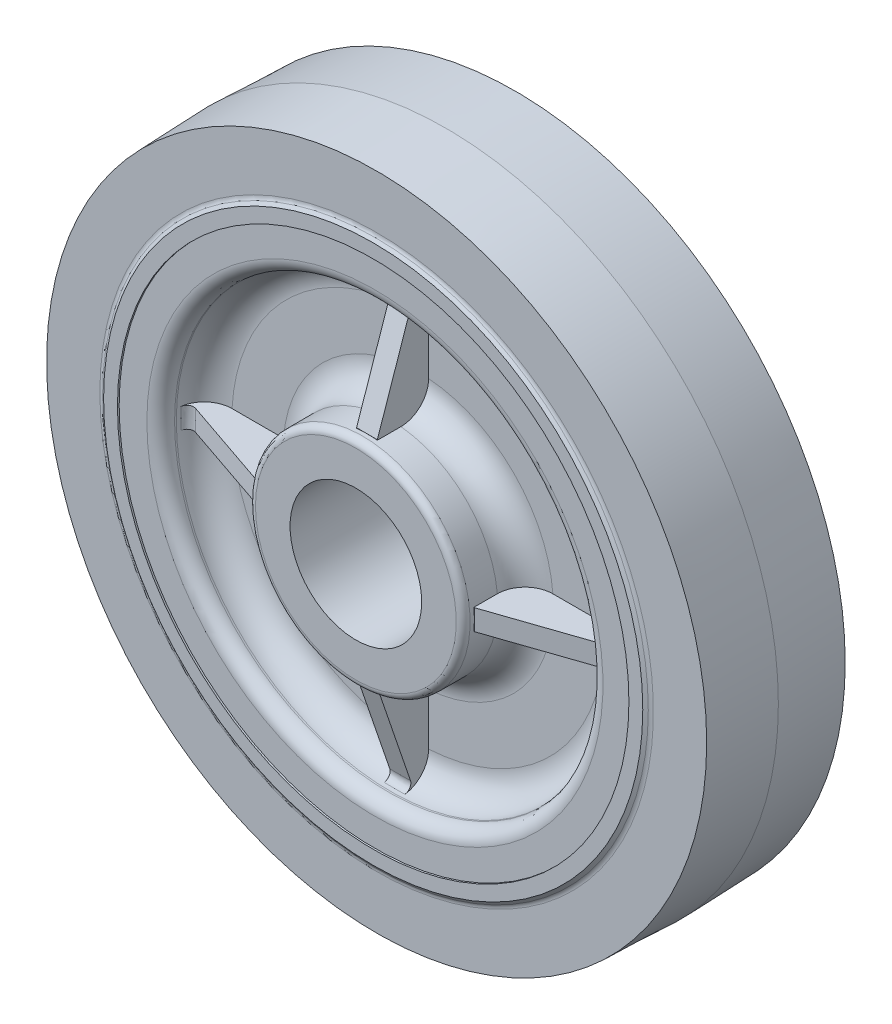
SolidWorks part; units mm, degrees
ref_plane "Front Plane" through (0, 0, 0) normal (0, 0, 1) x (1, 0, 0)
ref_plane "Top Plane" through (0, 0, 0) normal (0, 1, 0) x (1, 0, 0)
ref_plane "Right Plane" through (0, 0, 0) normal (1, 0, 0) x (0, 0, -1)
sketch "Sketch1" plane through (0, 0, 0) normal (1, 0, 0) x (0, 0, -1)
  line L0 (0, 0) -> (41.275, 0) construction
  line L1 (20.6375, 0) -> (20.6375, 76.2) construction
  line L2 (36.9094, 49.0909) -> (26.9875, 49.0909)
  line L3 (26.9875, 28.575) -> (14.2875, 28.575) construction
  line L4 (20.6375, 76.2) -> (36.5125, 75.6456)
  line L5 (36.5125, 75.6456) -> (36.5125, 62.9456)
  line L6 (36.5125, 62.9456) -> (37.3063, 61.7909)
  line L7 (37.3063, 61.7909) -> (37.3063, 58.6159)
  line L8 (37.3063, 58.6159) -> (36.9094, 58.6159)
  line L9 (36.9094, 58.6159) -> (36.9094, 49.0909)
  line L10 (4.3656, 49.0909) -> (14.2875, 49.0909)
  line L11 (14.2875, 49.0909) -> (14.2875, 24.6062)
  line L12 (4.3656, 58.6159) -> (4.3656, 49.0909)
  line L13 (3.9687, 58.6159) -> (4.3656, 58.6159)
  line L14 (3.9687, 61.7909) -> (3.9687, 58.6159)
  line L15 (4.7625, 62.9456) -> (3.9687, 61.7909)
  line L16 (4.7625, 75.6456) -> (4.7625, 62.9456)
  line L17 (26.9875, 49.0909) -> (26.9875, 24.6062)
  line L18 (20.6375, 76.2) -> (4.7625, 75.6456)
  line L19 (0, 15.0812) -> (41.275, 15.0812)
  line L20 (14.2875, 24.6062) -> (0, 24.6062)
  line L21 (0, 15.0812) -> (0, 24.6062)
  line L22 (26.9875, 24.6062) -> (41.275, 24.6062)
  line L23 (41.275, 15.0812) -> (41.275, 24.6062)
  point P9 (20.6375, 28.575)
  dimension "D1" = 41.275
  dimension "D2" = 76.2
  dimension "D3" = 9.525
  dimension "D4" = 12.7
  dimension "D6" = 88
  dimension "D7" = 15.875
  dimension "D8" = 12.7
  dimension "D9" = 0.7937
  dimension "D10" = 0.3969
  dimension "D11" = 3.175
  dimension "D12" = 9.525
  dimension "D13" = 15.0812
revolve "Revolve1" add sketch "Sketch1" angle 360 about L0
fillet "Fillet1" radius 6.35 2 edges at (49.0909, 0, -14.2875) (24.6062, 0, -14.2875)
fillet "Fillet2" radius 3.175 1 edges at (49.0909, 0, -4.3656)
fillet "Fillet3" radius 1.5875 1 edges at (62.9456, 0, -4.7625)
sketch "Sketch2" plane through (0, 0, 0) normal (0, 0, 1) x (1, 0, 0)
  line L1 (0, 0) -> (-76.2, 0) construction
  line L2 (0, 0) -> (0, 76.2) construction
  circle A1 centre (0, 0) radius 76.2 construction
ref_plane "Plane1" through (0, 0, 0) normal (-1, 0, 0) x (0, 0, 1)
sketch "Sketch4" plane through (0, 0, 0) normal (-1, 0, 0) x (0, 0, 1)
  line L1 (-20.6375, 76.2) -> (-20.6375, -76.2) construction
  line L2 (-20.6375, 15.0812) -> (-20.6375, 59.0132)
  line L3 (-2.54, 15.0812) -> (-2.54, 24.6062)
  line L4 (0, 24.6062) -> (-7.9375, 24.6062) construction
  line L5 (0, -24.6062) -> (0, 24.6062) construction
  line L6 (-2.54, 24.6062) -> (-14.2875, 59.0132)
  line L7 (-14.2875, 59.0132) -> (-20.6375, 59.0132)
  line L8 (-2.54, 15.0812) -> (-20.6375, 15.0812)
  dimension "D1" = 2.54
  dimension "D2" = 6.35
  dimension "D3" = 9.525
extrude "Boss-Extrude1" add sketch "Sketch4" along normal blind 2.3813 and the other way blind 2.3813
pattern_circular "CirPattern1" count 4 every 90 about axis through (0, 0, -20.6375) along (0, 0, 1) of "Boss-Extrude1"
fillet "Fillet4" radius 1.5875 4 edges
sketch "Sketch6" plane through (0, 0, 0) normal (-1, 0, 0) x (0, 0, 1)
  line L0 (-20.6375, 0) -> (-20.6375, 76.2) construction
  line L1 (-20.6375, 76.2) -> (-20.6375, -76.2) construction
ref_plane "Plane2" through (0, 0, -20.6375) normal (0, 0, 1) x (0, 1, 0)
fillet "Fillet7" radius 6.35 2 edges at (49.0909, 0, -26.9875) (24.6062, 0, -26.9875)
fillet "Fillet8" radius 1.5875 1 edges at (24.6062, 0, 0)
fillet "Fillet9" radius 1.5875 1 edges at (24.6062, 0, -41.275)
fillet "Fillet10" radius 3.175 1 edges at (49.0909, 0, -36.9094)
mirror "Mirror4" about plane through (0, 0, -20.6375) normal (0, 0, 1) of "CirPattern1", "Boss-Extrude1"
fillet "Fillet12" radius 1.5875 4 edges
